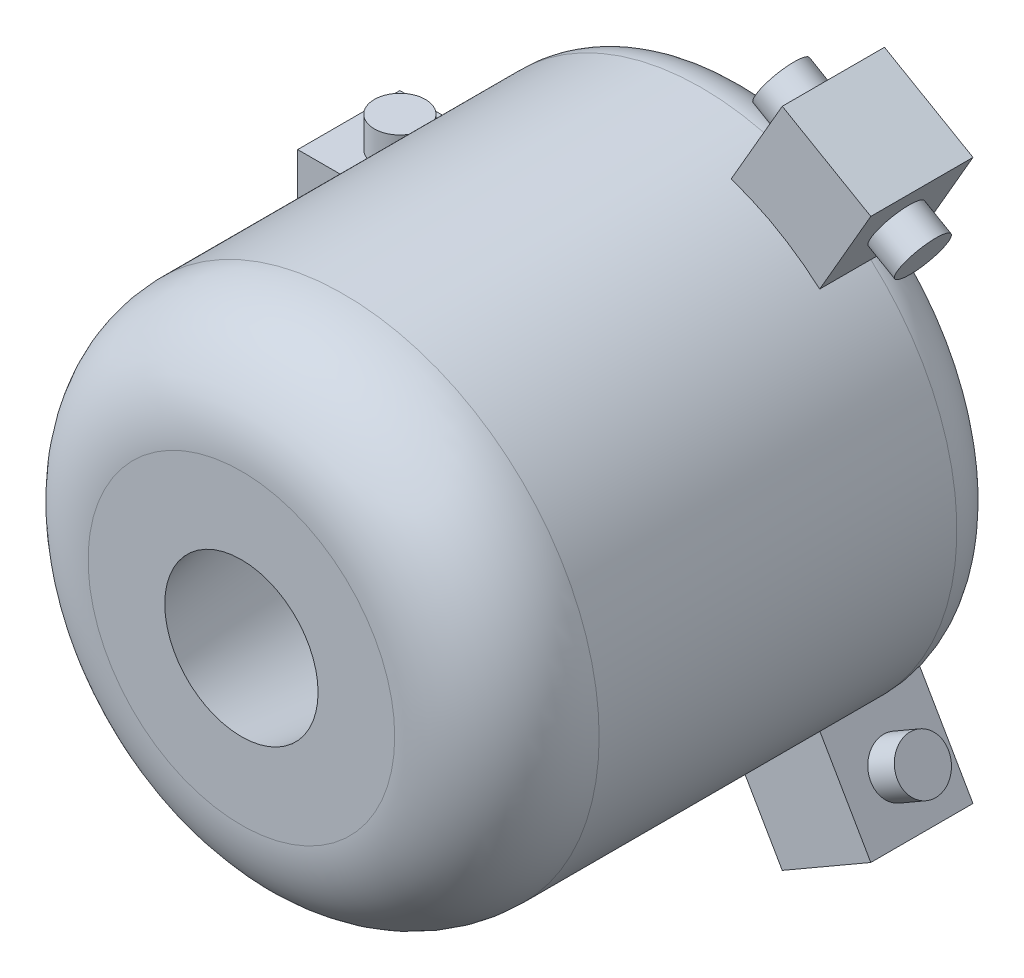
SolidWorks part; units mm, degrees
ref_plane "Front Plane" through (0, 0, 0) normal (0, 0, 1) x (1, 0, 0)
ref_plane "Top Plane" through (0, 0, 0) normal (0, 1, 0) x (1, 0, 0)
ref_plane "Right Plane" through (0, 0, 0) normal (1, 0, 0) x (0, 0, -1)
sketch "Sketch1" plane through (0, 0, 0) normal (0, 0, 1) x (1, 0, 0)
  line L0 (0, 0) -> (50, 0) construction
  line L1 (0, 0) -> (-25, 43.3013) construction
  line L2 (0, 0) -> (-25, -43.3013) construction
  circle A0 centre (0, 0) radius 25
  dimension "D6" = 50
  dimension "D1" = 50
  dimension "D2" = 50
  dimension "D3" = 50
  dimension "D4" = 120
  dimension "D5" = 120
extrude "Boss-Extrude1" add sketch "Sketch1" along normal blind 50
sketch "Sketch2" plane through (0, 0, 0) normal (0, 0, -1) x (-1, 0, 0)
  line L0 (0, 0) -> (50, 0) construction
  line L2 (34.4949, -5) -> (24.4949, -5)
  line L3 (34.4949, -5) -> (34.4949, 5)
  line L4 (34.4949, 5) -> (24.4949, 5)
  line L5 (24.4949, -5) -> (24.4949, 5)
  line L6 (34.4949, -5) -> (24.4949, 5) construction
  line L7 (34.4949, 5) -> (24.4949, -5) construction
  circle A0 centre (0, 0) radius 25 construction
  point P2 (29.4949, 0)
  dimension "D1" = 50
  dimension "D2" = 10
  dimension "D3" = 10
extrude "Boss-Extrude2" add sketch "Sketch2" against normal blind 10
sketch "Sketch3" plane through (0, -5, 0) normal (0, -1, 0) x (1, 0, 0)
  line L0 (-29.4949, 10) -> (-29.4949, 0) construction
  line L1 (-24.4949, 10) -> (-34.4949, 10) construction
  line L2 (-24.4949, 0) -> (-34.4949, 0) construction
  line L3 (-34.4949, 5) -> (-24.4949, 5) construction
  line L4 (-34.4949, 10) -> (-34.4949, 0) construction
  line L5 (-24.4949, 10) -> (-24.4949, 0) construction
  circle A0 centre (-29.4949, 5) radius 2.5
  dimension "D1" = 5
extrude "Boss-Extrude3" add sketch "Sketch3" along normal blind 3
sketch "Sketch4" plane through (0, 5, 0) normal (0, 1, 0) x (1, 0, 0)
  line L0 (-29.4949, 0) -> (-29.4949, -10) construction
  line L1 (-34.4949, 0) -> (-24.4949, 0) construction
  line L2 (-34.4949, -10) -> (-24.4949, -10) construction
  line L3 (-34.4949, -5) -> (-24.4949, -5) construction
  line L4 (-34.4949, -10) -> (-34.4949, 0) construction
  line L5 (-24.4949, -10) -> (-24.4949, 0) construction
  circle A0 centre (-29.4949, -5) radius 2.5
  dimension "D1" = 5
extrude "Boss-Extrude4" add sketch "Sketch4" along normal blind 3
pattern_circular "CirPattern1" count 3 over 360 about axis through (0, 0, 50) along (0, 0, -1) of "Boss-Extrude4", "Boss-Extrude2", "Boss-Extrude3"
sketch "Sketch5" plane through (0, 0, 50) normal (0, 0, 1) x (1, 0, 0)
  circle A0 centre (0, 0) radius 7.5
  dimension "D1" = 15
sketch "Sketch6" plane through (0, 0, 0) normal (0, 0, -1) x (-1, 0, 0)
  circle A0 centre (0, 0) radius 15
  dimension "D1" = 30
loft "Cut-Loft1" cut profiles "Sketch5", "Sketch6" connector at (-2.9523, 6.8945, 50) connector at (-5.8966, 13.7924, 0)
fillet "Fillet1" radius 10 1 edges at (25, 0, 50)
fillet "Fillet2" radius 5 3 edges at (-12.5, -21.6506, 0) (-12.5, 21.6506, 0) (25, 0, 0)
